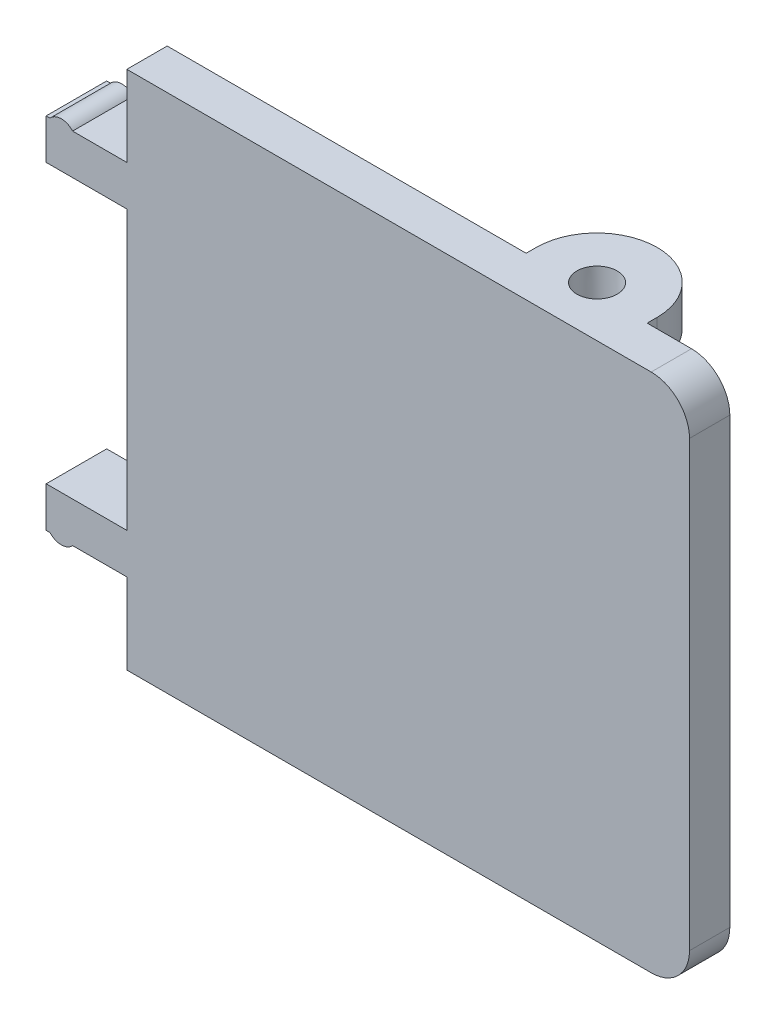
SolidWorks part; units mm, degrees
ref_plane "前视基准面" through (0, 0, 0) normal (0, 0, 1) x (1, 0, 0)
ref_plane "上视基准面" through (0, 0, 0) normal (0, 1, 0) x (1, 0, 0)
ref_plane "右视基准面" through (0, 0, 0) normal (1, 0, 0) x (0, 0, -1)
other "Configuration Table"
sketch "草图1" plane through (0, 0, 0) normal (0, 0, 1) x (1, 0, 0)
  line L3 (-11.9424, 3.3113) -> (-11.9424, -22.4887)
  line L4 (-11.9424, 37.4113) -> (-11.9424, -25.5887) construction
  line L6 (-11.9424, -22.4887) -> (14.0576, -22.4887)
  line L7 (15.9576, -20.5887) -> (15.9576, 1.4113)
  line L8 (14.0576, 3.3113) -> (-11.9424, 3.3113)
  line L9 (-11.9424, -22.4887) -> (14.0576, -22.4887)
  line L10 (15.9576, -20.5887) -> (15.9576, 1.4113)
  line L11 (14.0576, 3.3113) -> (-11.9424, 3.3113)
  arc A4 (14.0576, -22.4887) -> (15.9576, -20.5887) centre (14.0576, -20.5887) ccw
  arc A5 (15.9576, 1.4113) -> (14.0576, 3.3113) centre (14.0576, 1.4113) ccw
  arc A6 (14.0576, -22.4887) -> (15.9576, -20.5887) centre (14.0576, -20.5887) ccw
  arc A7 (15.9576, 1.4113) -> (14.0576, 3.3113) centre (14.0576, 1.4113) ccw
  dimension "D1" = 0.1
extrude "凸台-拉伸1" add sketch "草图1" against normal blind 2
sketch "草图2" plane through (0, 0, -2) normal (0, 0, -1) x (-1, 0, 0)
  line L0 (11.9424, -22.4887) -> (-14.0576, -22.4887) construction
  line L1 (-5.8576, -22.4887) -> (-11.8576, -22.4887)
  line L2 (-5.8576, -22.4887) -> (-5.8576, -20.4887)
  line L3 (-5.8576, -20.4887) -> (-11.8576, -20.4887)
  line L4 (-11.8576, -22.4887) -> (-11.8576, -20.4887)
  line L5 (-14.0576, 3.3113) -> (11.9424, 3.3113) construction
  line L6 (-5.8576, 3.3113) -> (-11.8576, 3.3113)
  line L7 (-5.8576, 3.3113) -> (-5.8576, 1.3113)
  line L8 (-5.8576, 1.3113) -> (-11.8576, 1.3113)
  line L9 (-11.8576, 3.3113) -> (-11.8576, 1.3113)
  line L10 (-18.0576, -20.5887) -> (-18.0576, 1.4113) construction
  dimension "D1" = 6
  dimension "D2" = 6.2
  dimension "D3" = 2
extrude "凸台-拉伸2" add sketch "草图2" along normal blind 3.5
fillet "圆角1" radius 3 4 edges at (11.8576, 2.3113, -5.5) (5.8576, 2.3113, -5.5) (11.8576, -21.4887, -5.5) (5.8576, -21.4887, -5.5)
sketch "草图3" plane through (0, -22.4887, 0) normal (0, -1, 0) x (1, 0, 0)
  circle A0 centre (8.8741, -2.5) radius 1
  dimension "D1" = 2
extrude "切除-拉伸1" cut sketch "草图3" against normal blind 5 draft 2
sketch "草图4" plane through (0, 3.3113, 0) normal (0, 1, 0) x (1, 0, 0)
  circle A0 centre (8.8741, 2.5) radius 1
  dimension "D1" = 2
extrude "切除-拉伸2" cut sketch "草图4" against normal blind 5 draft 2
sketch "草图6" plane through (0, 0, 0) normal (0, 0, 1) x (1, 0, 0)
  line L0 (-11.9424, 3.3113) -> (-11.9424, -22.4887) construction
  line L1 (-11.9424, -0.6887) -> (-15.9424, -0.6887)
  line L2 (-11.9424, -0.6887) -> (-11.9424, -2.6887)
  line L3 (-11.9424, -2.6887) -> (-15.9424, -2.6887)
  line L4 (-15.9424, -0.6887) -> (-15.9424, -2.6887)
  line L5 (14.0576, 3.3113) -> (-11.9424, 3.3113) construction
  line L6 (-11.9424, -18.4887) -> (-15.9424, -18.4887)
  line L7 (-11.9424, -18.4887) -> (-11.9424, -16.4887)
  line L8 (-11.9424, -16.4887) -> (-15.9424, -16.4887)
  line L9 (-15.9424, -18.4887) -> (-15.9424, -16.4887)
  line L10 (-11.9424, -22.4887) -> (14.0576, -22.4887) construction
  dimension "D1" = 2
  dimension "D2" = 4
  dimension "D3" = 4
  dimension "D4" = 4
extrude "凸台-拉伸3" add sketch "草图6" against normal blind 3
chamfer "倒角1" distance 3 angle 45 2 edges at (-11.9424, -17.4887, -2) (-11.9424, -1.6887, -2)
sketch "草图7" plane through (0, 0, 0) normal (0, 0, 1) x (1, 0, 0)
  line L0 (-15.9424, -0.6887) -> (-15.9424, -2.6887) construction
  line L1 (-15.9424, -2.6887) -> (-11.9424, -2.6887) construction
  line L2 (-15.9424, -16.4887) -> (-15.9424, -18.4887) construction
  line L3 (-11.9424, -16.4887) -> (-15.9424, -16.4887) construction
  circle A0 centre (-15.1924, -1.1887) radius 0.75
  circle A1 centre (-15.1924, -17.9887) radius 0.75
  dimension "D1" = 1.5
  dimension "D3" = 1.5
  dimension "D2" = 1.5
extrude "凸台-拉伸4" add sketch "草图7" against normal blind 3
